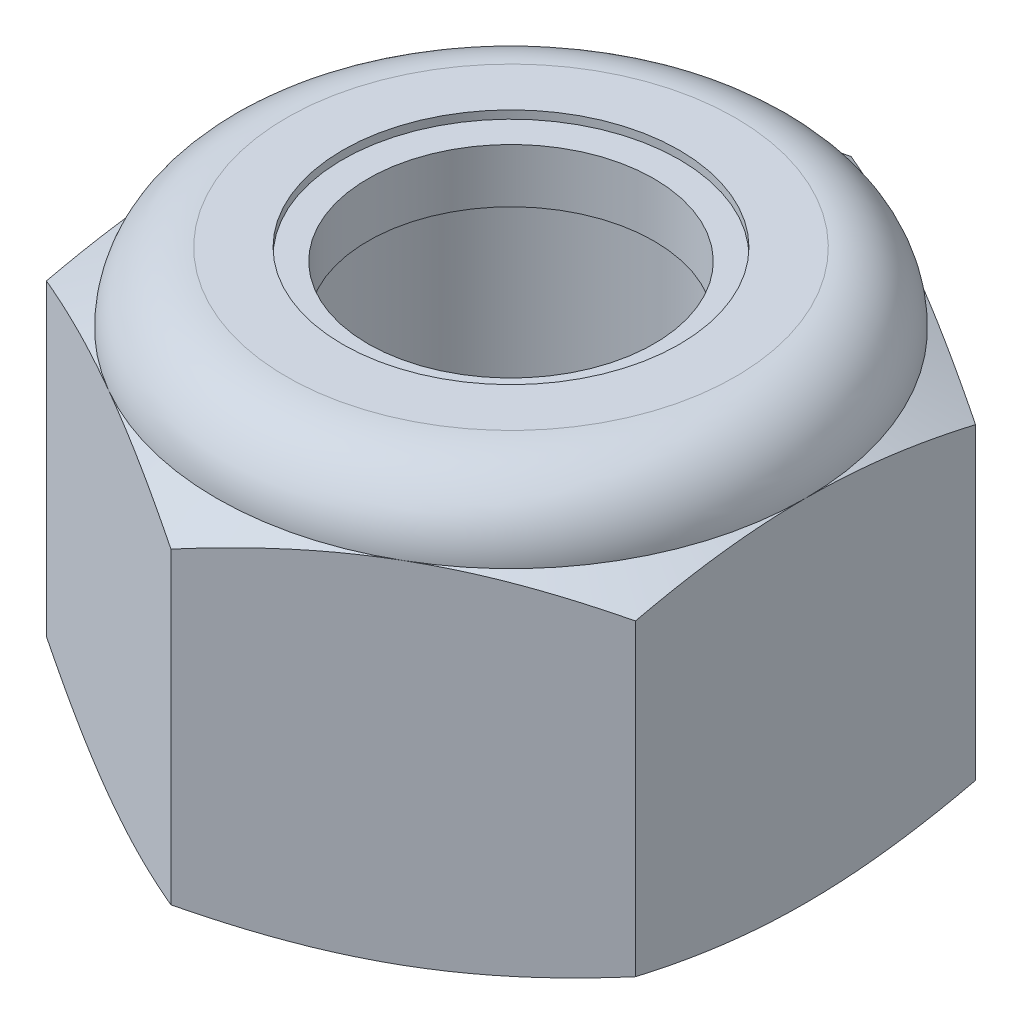
SolidWorks part; units mm, degrees
ref_plane "Front" through (0, 0, 0) normal (0, 0, 1) x (1, 0, 0)
ref_plane "Top" through (0, 0, 0) normal (0, 1, 0) x (1, 0, 0)
ref_plane "Right" through (0, 0, 0) normal (1, 0, 0) x (0, 0, -1)
sketch "Sketch8" plane through (0, 0, 0) normal (1, 0, 0) x (0, 0, -1)
  line L0 (0, 0) -> (0, 7.9375) construction
  line L1 (5.5562, 0) -> (-5.5562, 0) construction
  line L2 (-3.175, 7.9375) -> (3.175, 7.9375) construction
  line L3 (3.175, 7.9375) -> (3.175, 6.6675) construction
  point P7 (-2.6987, 7.9375)
  dimension "D1" = 5.3975
sketch "Sketch1" plane through (0, 0, 0) normal (0, 1, 0) x (1, 0, 0)
  line L1 (0, 6.4158) -> (-5.5563, 3.2079)
  line L2 (-5.5563, 3.2079) -> (-5.5562, -3.2079)
  line L3 (-5.5562, -3.2079) -> (0, -6.4158)
  line L4 (0, -6.4158) -> (5.5563, -3.2079)
  line L5 (5.5563, -3.2079) -> (5.5563, 3.2079)
  line L6 (5.5563, 3.2079) -> (0, 6.4158)
  circle A0 centre (0, 0) radius 5.5562 construction
  circle A1 centre (0, 0) radius 3.175
extrude "Extrude1" add sketch "Sketch1" along normal up to vertex (7.9375 mm away) up to point (0, 7.9375, 0)
sketch "Sketch5" plane through (0, 0, 0) normal (1, 0, 0) x (0, 0, -1)
  line L0 (0, 0) -> (5.5562, 0)
  line L1 (5.5562, 0) -> (6.4158, 0.4008)
  line L2 (6.4158, 0.4008) -> (6.4158, 6.2138)
  line L3 (6.4158, 6.2138) -> (5.5562, 6.6146)
  line L4 (4.2333, 7.9375) -> (4.2333, 9.2075)
  line L5 (4.2333, 9.2075) -> (7.6858, 9.2075)
  line L6 (7.6858, 9.2075) -> (7.6858, -1.27)
  line L7 (7.6858, -1.27) -> (0, -1.27)
  line L8 (0, -1.27) -> (0, 0)
  line L9 (5.5562, 6.6146) -> (5.5562, 0) construction
  line L12 (6.4158, 7.9375) -> (6.4158, 0) construction
  line L13 (6.4158, 3.9688) -> (7.6858, 3.9688) construction
  line L15 (0, 0) -> (0, 9.2075) construction
  line L18 (5.5562, 0) -> (-5.5562, 0) construction
  line L19 (3.2079, 7.9375) -> (6.4158, 7.9375) construction
  line L20 (0, 9.2075) -> (4.2333, 9.2075) construction
  line L21 (3.2079, 0) -> (6.4158, 0) construction
  arc A0 (5.5562, 6.6146) -> (4.2333, 7.9375) centre (4.2333, 6.6146) ccw
  dimension "D1" = 25
  dimension "D2" = 1.27
  dimension "D4" = 1.3229
revolve "Cut-Revolve3" cut sketch "Sketch5" angle 360 about L15
sketch "Sketch4" plane through (0, 0, 0) normal (1, 0, 0) x (0, 0, -1)
  line L0 (0, 6.6146) -> (3.4925, 6.6146)
  line L1 (3.4925, 6.6146) -> (0, 4.986)
  line L3 (0, 1.6286) -> (3.4925, 0)
  line L4 (3.4925, 0) -> (0, 0)
  line L5 (0, 0) -> (0, 6.6146) construction
  line L10 (0, 0) -> (0, 7.9375) construction
  line L11 (0, 1.6286) -> (0, 0)
  line L12 (0, 6.6146) -> (0, 4.986)
  line L13 (4.8119, 6.6146) -> (0, 6.6146) construction
  dimension "D1" = 25
  dimension "D2" = 6.985
sketch "Sketch6" plane through (0, 0, 0) normal (1, 0, 0) x (0, 0, -1)
  line L0 (0, 6.6146) -> (5.4039, 6.6146)
  line L1 (4.2333, 7.7851) -> (2.1167, 7.7851)
  line L2 (0, 9.2075) -> (0, 6.6146)
  line L3 (2.1167, 9.2075) -> (0, 9.2075)
  line L4 (0, 9.2075) -> (4.2333, 9.2075) construction
  line L5 (0, 0) -> (0, 9.2075) construction
  line L6 (0, 9.2075) -> (0, 0) construction
  line L7 (2.1167, 7.7851) -> (2.1167, 9.2075)
  line L8 (4.2333, 7.9375) -> (4.2333, 7.7851) construction
  line L9 (2.1167, 7.7851) -> (0, 7.7851) construction
  line L10 (0, 7.7851) -> (0, 4.986) construction
  arc A0 (5.4039, 6.6146) -> (4.2333, 7.7851) centre (4.2333, 6.6146) ccw
  arc A1 (5.5562, 6.6146) -> (4.2333, 7.9375) centre (4.2333, 6.6146) ccw construction
  dimension "D1" = 0.1524
revolve "Cut-Revolve4" cut sketch "Sketch6" angle 360 about L6
revolve "Cut-Revolve2" cut sketch "Sketch4" angle 360 about L5
sketch "Sketch7" plane through (0, 0, 0) normal (1, 0, 0) x (0, 0, -1)
  line L0 (2.6988, 6.6908) -> (5.325, 6.6908)
  line L1 (4.2333, 7.7089) -> (2.6988, 7.7089)
  line L2 (2.6988, 7.7089) -> (2.6988, 6.6908)
  line L3 (2.6988, 6.6908) -> (0, 6.6908) construction
  line L4 (0, 6.6908) -> (0, 7.7089) construction
  line L5 (0, 7.7089) -> (2.6988, 7.7089) construction
  line L6 (2.6988, 6.6908) -> (2.6988, 6.6146) construction
  line L7 (0, 6.6146) -> (5.4039, 6.6146) construction
  line L8 (4.2333, 7.7089) -> (4.2333, 7.7851) construction
  arc A0 (5.325, 6.6908) -> (4.2333, 7.7089) centre (4.2333, 6.6146) ccw
  arc A2 (5.4039, 6.6146) -> (4.2333, 7.7851) centre (4.2333, 6.6146) ccw construction
  dimension "D1" = 0.0762
  dimension "D2" = 5.3975
revolve "Revolve2" add sketch "Sketch7" angle 360 about L4
sketch "Sketch2" [suppressed] plane through (0, 0, 0) normal (1, 0, 0) x (0, 0, -1)
  line L0 (-3.175, 0) -> (-3.175, 6.6146) construction
  line L1 (0, 0) -> (3.175, 0)
  line L2 (0, 0) -> (0, 6.6146)
  line L3 (0, 6.6146) -> (3.175, 6.6146)
  line L4 (3.175, 0) -> (3.175, 6.6146)
  line L6 (4.8119, 6.6146) -> (5.5562, 6.6146) construction
  line L7 (0, -3.175) -> (0, 0) construction
revolve "Revolve1" [suppressed] add sketch "Sketch2" angle 360 about L7
sketch "Sketch9" [suppressed] plane through (0, 0, 0) normal (1, 0, 0) x (0, 0, -1)
  line L0 (3.3125, 7.8052) -> (3.3125, 6.5352) construction
  line L1 (3.3125, 6.5352) -> (2.2126, 7.1702) construction
  line L2 (2.2126, 7.1702) -> (3.3125, 7.8052) construction
  line L3 (2.3501, 7.2496) -> (2.3501, 7.0908) construction
  line L4 (3.175, 7.7258) -> (3.175, 6.6146) construction
  line L5 (2.2126, 7.1702) -> (2.3501, 7.1702) construction
  line L6 (3.175, 7.1702) -> (3.3125, 7.1702) construction
  line L7 (3.2437, 7.1702) -> (3.2437, 7.7655) construction
  line L8 (3.3125, 6.5352) -> (3.2437, 7.7655)
  line L9 (3.2437, 7.7655) -> (2.3501, 7.2496)
  line L10 (2.3501, 7.2496) -> (2.3501, 7.0908)
  line L11 (2.3501, 7.0908) -> (3.3125, 6.5352)
  dimension "D1" = 1.27
  dimension "D2" = 0.1588
sketch "Sketch10" [suppressed] plane through (0, 6.6146, 0) normal (0, 1, 0) x (1, 0, 0)
  circle A1 centre (0, 0) radius 3.175
  circle A2 centre (0, 0) radius 3.175
  dimension "D1" = 0
curve "Helix/Spiral1" [suppressed] pitch 1.27 height 9.2075 turns 7.25
sweep "Cut-Sweep1" [suppressed] cut profiles "Sketch9" path "Helix/Spiral1"
sketch "Sketch11" [suppressed] plane through (0, 0, 0) normal (1, 0, 0) x (0, 0, -1)
  line L0 (0, 0) -> (0, 7.9375) construction
  line L1 (5.5562, 0) -> (-5.5562, 0) construction
  line L4 (0, 7.9375) -> (0, 0) construction
  line L5 (0, 3.9688) -> (3.175, 3.9688) construction
  line L6 (0, 0) -> (3.4925, 0)
  line L7 (0, 1.6286) -> (0, 0)
  line L8 (3.4925, 0) -> (0, 1.6286)
  dimension "D1" = 6.985
  dimension "D2" = 25
revolve "Revolve3" [suppressed] add sketch "Sketch11" angle 360 about L4
sketch "Sketch12" [suppressed] plane through (0, 0, 0) normal (1, 0, 0) x (0, 0, -1)
  line L0 (3.4925, 6.6146) -> (0, 6.6146)
  line L1 (0, 6.6146) -> (0, 0)
  line L2 (0, 0) -> (3.4925, 0)
  line L3 (5.5562, 0) -> (-5.5562, 0) construction
  line L4 (3.4925, 0) -> (3.4925, 6.6146)
  line L5 (-3.4925, 0) -> (3.4925, 0) construction
revolve "Revolve4" [suppressed] add sketch "Sketch12" angle 360 about L0
combine bodies "Combine1" [suppressed] operation type subtract main body 136 bodies to subtract 133
equation "\"D4@Sketch5\"=\"Height@Sketch8\"/6"
equation "\"D1@Sketch9\"=\"Thread Pitch@Sketch8\""
equation "\"D2@Sketch9\"=\"Thread Pitch@Sketch8\"/8"
equation "\"D4@Helix/Spiral1\"=\"Thread Pitch@Sketch8\""
equation "\"D3@Helix/Spiral1\"=\"Thread Pitch@Sketch8\"+\"Height@Sketch8\""
equation "\"D2@Sketch4\"=\"Thread Dia@Sketch8\"*1.1"
equation "\"D1@Sketch11\"=\"Thread Dia@Sketch8\"*1.1"
equation "\"D2@Sketch7\"=\"Thread Dia@Sketch8\"*.85"
equation "\"D1@Sketch8\"=\"Thread Dia@Sketch8\"*.85"
